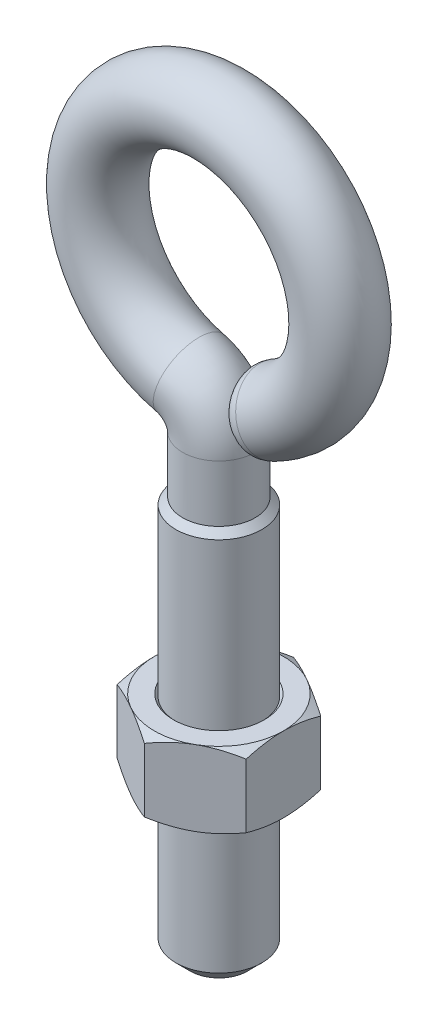
SolidWorks part; units mm, degrees
material "Plain Carbon Steel"
ref_plane "Front Plane" through (0, 0, 0) normal (0, 0, 1) x (1, 0, 0)
ref_plane "Top Plane" through (0, 0, 0) normal (0, 1, 0) x (1, 0, 0)
ref_plane "Right Plane" through (0, 0, 0) normal (1, 0, 0) x (0, 0, -1)
sketch "Sketch1" plane through (0, 0, 0) normal (0, 0, 1) x (1, 0, 0)
  line L0 (0, -8.636) -> (0, -34.036) construction
  line L1 (-2.413, -34.036) -> (2.413, -34.036) construction
  line L2 (0, -11.811) -> (2.413, -11.811) construction
  line L3 (0, -8.636) -> (0, -4.7625) construction
  line L4 (-2.032, -11.811) -> (2.032, -11.811) construction
  line L5 (2.032, -11.811) -> (2.032, -8.636) construction
  line L7 (2.413, -34.036) -> (2.413, -11.811) construction
  line L8 (2.032, -8.636) -> (0, -8.636) construction
  circle A0 centre (0, 0) radius 8.8265 construction
  circle A1 centre (0, 6.7945) radius 2.032 construction
  circle A2 centre (0, 0) radius 4.7625 construction
  point P9 (0, -8.636)
  point P10 (0, 8.8265)
  point P11 (0, 4.7625)
  point P14 (0, -34.036)
  point P24 (0, -11.811)
sketch "Sketch2" plane through (0, 0, 0) normal (0, 1, 0) x (1, 0, 0)
  circle A0 centre (0, 0) radius 2.413
extrude "Boss-Extrude1" add sketch "Sketch2" against normal up to vertex (34.036 mm away) from vertex up to point (0, -34.036, 0) starting at point (0, -11.811, 0)
sketch "Sketch3" plane through (0, -34.036, 0) normal (0, -1, 0) x (1, 0, 0)
  circle A1 centre (0, 0) radius 2.413
  circle A2 centre (0, 0) radius 2.413
  point P0 (2.413, 0)
  point P1 (0, -2.413)
  dimension "D1" = 0
curve "Helix/Spiral1" [suppressed] pitch 1.0583 height 23.2833 turns 22 parameters "Pitch"=1.0583
sketch "Sketch4" plane through (0, 0, 0) normal (0, 0, 1) x (1, 0, 0)
  line L0 (2.5276, -33.9699) -> (2.5276, -35.0282) construction
  line L1 (2.5276, -35.0282) -> (1.611, -34.499) construction
  line L2 (1.611, -34.499) -> (2.5276, -33.9699) construction
  line L3 (1.7256, -34.4329) -> (1.7256, -34.5652) construction
  line L4 (2.413, -34.036) -> (2.413, -34.962) construction
  line L5 (1.611, -34.499) -> (1.7256, -34.499) construction
  line L6 (2.413, -34.499) -> (2.5276, -34.499) construction
  line L7 (2.4703, -34.0029) -> (1.7256, -34.4329)
  line L8 (1.7256, -34.4329) -> (1.7256, -34.5652)
  line L9 (1.7256, -34.5652) -> (2.4703, -34.9951)
  line L10 (2.4703, -34.9951) -> (2.4703, -34.0029)
  point P13 (2.4703, -34.499)
  dimension "D1" = 1.0583
  dimension "D2" = 0.1323
sweep "Cut-Sweep1" [suppressed] cut profiles "Sketch4" path "Helix/Spiral1"
sketch "Sketch5" plane through (0, -34.036, 0) normal (0, -1, 0) x (1, 0, 0)
  circle A0 centre (0, 0) radius 1.611
extrude "Cut-Extrude1" cut sketch "Sketch5" against normal up to vertex (22.225 mm away) draft 45 flip side to cut up to point (0, -11.811, 0)
sketch "Sketch7" plane through (0, -11.811, 0) normal (0, 1, 0) x (1, 0, 0)
  circle A0 centre (0, 0) radius 2.032
sketch "Sketch8" plane through (0, 0, 0) normal (0, 0, 1) x (1, 0, 0)
  line L0 (0, -8.636) -> (0, -34.036) construction
  line L1 (0, -8.636) -> (0, -11.811)
  line L2 (0, -8.636) -> (0, -4.7625) construction
  arc A0 (2.0092, -6.4906) -> (-1.599, -6.6037) centre (0, 0) ccw
  arc A1 (0, -8.636) -> (-1.599, -6.6037) centre (-2.091, -8.636) ccw
  circle A3 centre (0, -6.7945) radius 2.032 construction
sketch "Sketch6" plane through (0, -11.811, 0) normal (0, 1, 0) x (1, 0, 0)
  circle A0 centre (0, 0) radius 2.032
extrude "Cut-Extrude2" cut sketch "Sketch6" against normal up to vertex (22.225 mm away) draft 45 flip side to cut up to point (0, -34.036, 0)
sweep "Sweep1" add profiles "Sketch7" path "Sketch8"
fillet "Fillet1" radius 1.2065 1 edges at (2.0092, -6.4906, 2.032)
sketch "Sketch9" plane through (0, -34.036, 0) normal (0, -1, 0) x (1, 0, 0)
  line L1 (0, 4.1794) -> (-3.6195, 2.0897)
  line L2 (-3.6195, 2.0897) -> (-3.6195, -2.0897)
  line L3 (-3.6195, -2.0897) -> (0, -4.1794)
  line L4 (0, -4.1794) -> (3.6195, -2.0897)
  line L5 (3.6195, -2.0897) -> (3.6195, 2.0897)
  line L6 (3.6195, 2.0897) -> (0, 4.1794)
  circle A0 centre (0, 0) radius 3.6195 construction
  circle A1 centre (0, 0) radius 2.413
extrude "Boss-Extrude2" add sketch "Sketch9" against normal blind 4.2227 from offset 8.4455 separate body offset against normal yes
sketch "Sketch10" plane through (0, 0, 0) normal (1, 0, 0) x (0, 0, -1)
  line L0 (-3.6195, -21.3677) -> (-4.7394, -21.3677)
  line L1 (-4.7394, -21.3677) -> (-4.7394, -25.5905)
  line L2 (-4.7394, -25.5905) -> (-3.6195, -25.5905)
  line L3 (-3.6195, -25.5905) -> (-4.1794, -25.2672)
  line L4 (-4.1794, -25.2672) -> (-4.1794, -21.691)
  line L5 (-4.1794, -21.691) -> (-3.6195, -21.3677)
  line L6 (-2.2807, -21.3677) -> (-2.2807, -25.5905)
  line L7 (-2.2807, -25.5905) -> (-2.5453, -25.5905)
  line L8 (-2.5453, -25.5905) -> (-2.413, -25.4582)
  line L9 (-2.413, -25.4582) -> (-2.413, -21.5)
  line L10 (-2.413, -21.5) -> (-2.5453, -21.3677)
  line L11 (-2.5453, -21.3677) -> (-2.2807, -21.3677)
  line L12 (-2.413, -21.3677) -> (-2.413, -25.5905) construction
  line L14 (-2.413, -25.4582) -> (-2.413, -25.5905) construction
  line L15 (-2.413, -21.5) -> (-2.413, -21.3677) construction
  line L16 (-4.1794, -21.3677) -> (-4.1794, -25.5905) construction
  line L18 (-3.6195, -25.5905) -> (-3.6195, -34.036) construction
  dimension "D1" = 60
  dimension "D2" = 45
  dimension "D3" = 0.1323
revolve "Cut-Revolve1" cut sketch "Sketch10" angle 360 about L0
sketch "SketchX" plane through (0, 0, 0) normal (1, 0, 0) x (0, 0, -1)
  line L0 (2.413, -34.036) -> (2.413, -15.7797) construction
  dimension "D1" = 18.2562
equation "\"D3@Helix/Spiral1\" = \"Pitch@Helix/Spiral1\" + \"Thread Lg.@Sketch1\""
equation "\"D1@Sketch4\" = \"Pitch@Helix/Spiral1\""
equation "\"A@Sketch1\" = \"Wire OD.@Sketch1\""
equation "\"D2@Sketch4\" = \"D1@Sketch4\" / 8"
equation "\"D1@Fillet1\" = \"Thread OD@Sketch1\" / 4"
equation "\"D1@SketchX\" = \"Thread Lg.@Sketch1\" -  ( \"Pitch@Helix/Spiral1\" *  4 ) +  ( \"Pitch@Helix/Spiral1\" /  4 ) "
equation "\"Nut Wd.@Sketch9\" = \"Thread OD@Sketch1\" * 1.5"
equation "\"Nut Ht.@Boss-Extrude2\" = \"Thread OD@Sketch1\" * 0.875"
equation "\"Offset@Boss-Extrude2\" = \"Nut Ht.@Boss-Extrude2\" * 2"
equation "\"D3@Sketch10\" = \"Pitch@Helix/Spiral1\" / 8"
